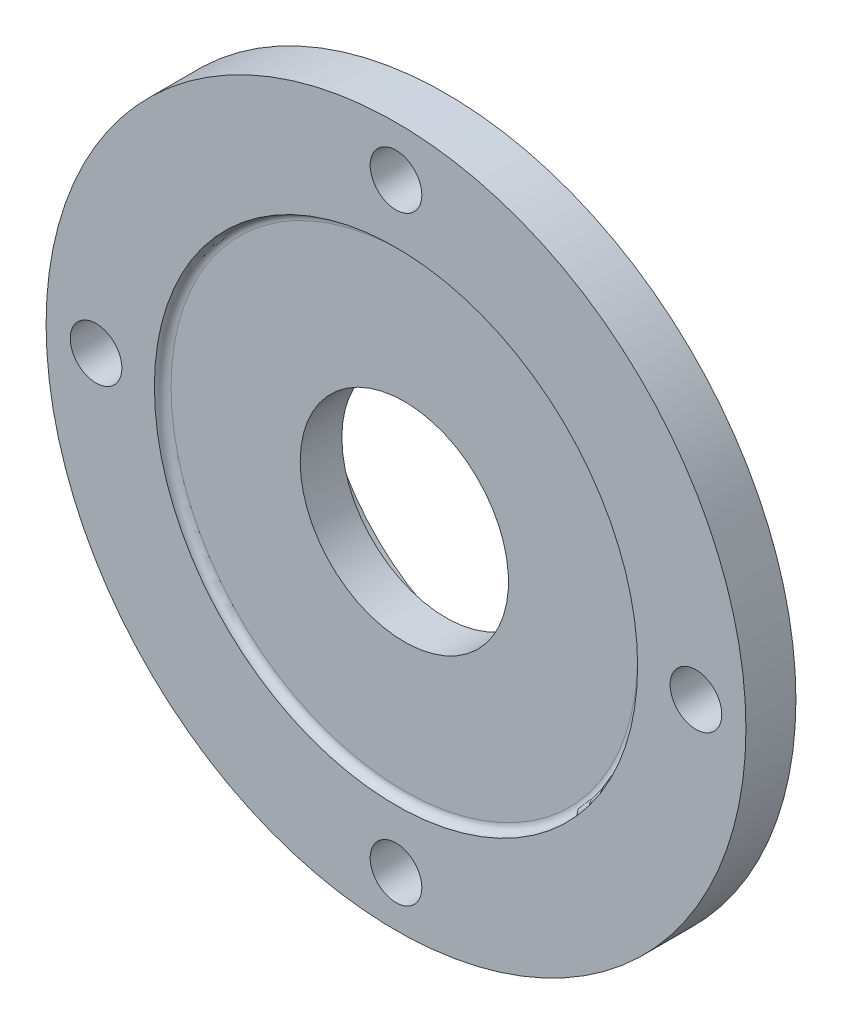
SolidWorks part; units mm, degrees
ref_plane "Спереди" through (0, 0, 0) normal (0, 0, 1) x (1, 0, 0)
ref_plane "Сверху" through (0, 0, 0) normal (0, 1, 0) x (1, 0, 0)
ref_plane "Справа" through (0, 0, 0) normal (1, 0, 0) x (0, 0, -1)
sketch "Эскиз1" plane through (0, 0, 0) normal (0, 0, 1) x (1, 0, 0)
  circle A0 centre (0, 0) radius 42
  circle A1 centre (0, 36) radius 3.1
  circle A2 centre (36, 0) radius 3.1
  circle A3 centre (0, -36) radius 3.1
  circle A4 centre (-36, 0) radius 3.1
  point P14 (0, 0)
  dimension "D1" = 84
  dimension "D2" = 6.2
  dimension "D3" = 36
  dimension "D4" = 4
extrude "Бобышка-Вытянуть1" add sketch "Эскиз1" along normal blind 6
sketch "Эскиз2" plane through (0, 0, 6) normal (0, 0, 1) x (1, 0, 0)
  circle A0 centre (0, 0) radius 29
  dimension "D1" = 58
extrude "Вырез-Вытянуть1" cut sketch "Эскиз2" against normal blind 1
fillet "Скругление3" radius 1 1 edges at (29, 0, 5)
sketch "Эскиз3" plane through (0, 0, 0) normal (0, 0, -1) x (-1, 0, 0)
  circle A0 centre (0, 0) radius 29
  circle A1 centre (0, 0) radius 23.5
  dimension "D1" = 58
  dimension "D2" = 47
extrude "Бобышка-Вытянуть2" add sketch "Эскиз3" along normal blind 8.3
chamfer "Фаска1" distance 1 angle 45 1 edges at (-23.5, 0, 0)
sketch "Эскиз4" plane through (0, 0, 0) normal (0, 0, -1) x (-1, 0, 0)
  circle A0 centre (0, 0) radius 12.5
  dimension "D1" = 25
extrude "Вырез-Вытянуть2" cut sketch "Эскиз4" against normal blind 8.3
